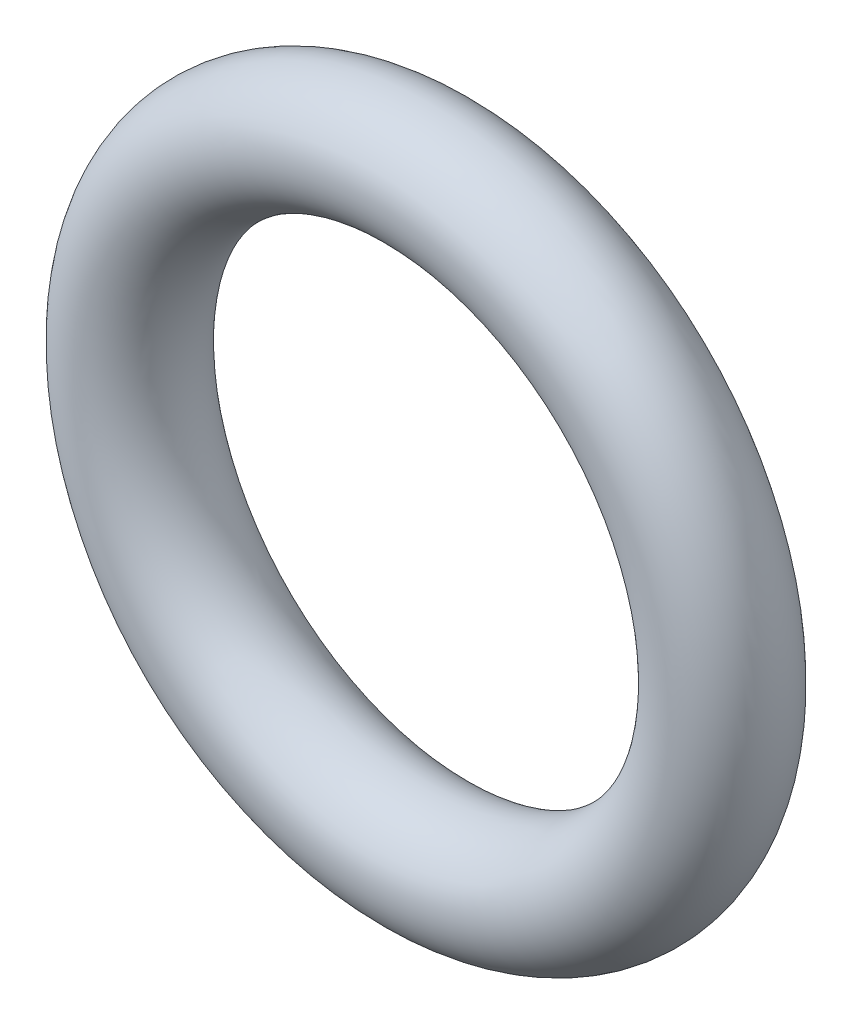
SolidWorks part; units mm, degrees
ref_plane "Front Plane" through (0, 0, 0) normal (0, 0, 1) x (1, 0, 0)
ref_plane "Top Plane" through (0, 0, 0) normal (0, 1, 0) x (1, 0, 0)
ref_plane "Right Plane" through (0, 0, 0) normal (1, 0, 0) x (0, 0, -1)
sketch "Sketch1" plane through (0, 0, 0) normal (1, 0, 0) x (0, 0, -1)
  circle A0 centre (0, 0) radius 1.6867
  dimension "D1" = 3.3734
sketch "Sketch2" plane through (0, 0, 0) normal (0, 0, 1) x (1, 0, 0)
  circle A0 centre (0, -8.4336) radius 8.4336
  dimension "D1" = 16.8672
sweep "Sweep1" add profiles "Sketch1" path "Sketch2"
